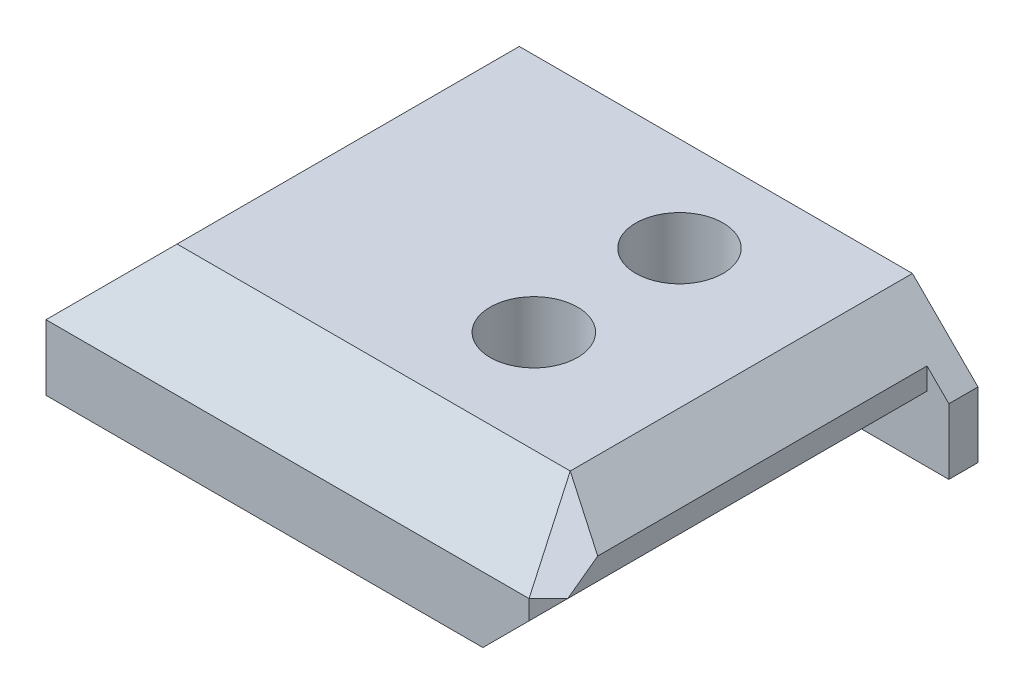
SolidWorks part; units mm, degrees
ref_plane "Front Plane" through (0, 0, 0) normal (0, 0, 1) x (1, 0, 0)
ref_plane "Top Plane" through (0, 0, 0) normal (0, 1, 0) x (1, 0, 0)
ref_plane "Right Plane" through (0, 0, 0) normal (1, 0, 0) x (0, 0, -1)
sketch "Sketch1" plane through (0, 0, 0) normal (0, 0, 1) x (1, 0, 0)
  line L0 (0, 0) -> (0, 9)
  line L1 (0, 9) -> (36, 9)
  line L2 (36, 9) -> (36, 0)
  line L3 (55, 0) -> (-55, 0) construction
  line L4 (36, 0) -> (0, 0)
extrude "Boss-Extrude1" add sketch "Sketch1" along normal blind 28
ref_plane "Plane1" through (0, 4.5, 0) normal (0, -1, 0) x (-1, 0, 0)
sketch "Sketch2" plane through (0, 0, 0) normal (0, 0, 1) x (1, 0, 0)
  line L0 (0, 4.5) -> (4.5, 9)
  line L1 (0, 9) -> (0, 0) construction
  line L2 (36, 9) -> (0, 9) construction
  line L3 (0, 4.5) -> (0, 9)
  line L4 (0, 9) -> (4.5, 9)
  line L5 (18, 10.7859) -> (18, -2.0026) construction
  line L6 (36, 4.5) -> (31.5, 9)
  line L7 (36, 4.5) -> (36, 9)
  line L8 (36, 9) -> (31.5, 9)
extrude "Cut-Extrude1" cut sketch "Sketch2" along normal blind 28
sketch "Sketch3" plane through (0, 0, 0) normal (1, 0, 0) x (0, 0, -1)
  line L0 (-28, 4.5) -> (-23.5, 9)
  line L1 (-28, 4.5) -> (0, 4.5) construction
  line L2 (-28, 0) -> (-28, 4.5) construction
  line L3 (-28, 9) -> (0, 9) construction
  line L4 (-28, 4.5) -> (-28, 9)
  line L5 (-28, 9) -> (-23.5, 9)
extrude "Cut-Extrude2" cut sketch "Sketch3" along normal blind 36
ref_plane "Plane2" through (32, 0, 32) normal (0.7071, 0, 0.7071) x (0, 1, 0)
sketch "Sketch5" plane through (32, 0, 32) normal (0.7071, 0, 0.7071) x (0, 1, 0)
  line L0 (0, -15.4) -> (0, 15.4) construction
  line L1 (0, 1.8738) -> (11.4404, 1.8738)
  line L2 (0, 1.8738) -> (0, -13.7452)
  line L3 (0, -13.7452) -> (11.4404, -13.7452)
  line L4 (11.4404, 1.8738) -> (11.4404, -13.7452)
extrude "Cut-Extrude4" cut sketch "Sketch5" against normal blind 2
ref_plane "Plane3" through (4, 0, -4) normal (-0.7071, 0, 0.7071) x (0.5774, -0.5774, 0.5774)
sketch "Sketch6" plane through (4, 0, -4) normal (-0.7071, 0, 0.7071) x (0.5774, -0.5774, 0.5774)
  line L0 (26.5581, 29.8021) -> (32.7193, 28.6474)
  line L1 (32.7193, 28.6474) -> (30.1986, 32.2123)
  line L2 (30.1986, 32.2123) -> (26.5581, 29.8021)
extrude "Cut-Extrude5" cut sketch "Sketch6" against normal blind 2 and the other way blind 2
sketch "Sketch7" plane through (0, 0, 0) normal (0, 0, 1) x (1, 0, 0)
  line L0 (0, 0) -> (5, 0) construction
  line L1 (15.4226, 0) -> (-15.4226, 0) construction
  line L2 (5, 0) -> (5, 3)
  line L3 (5, 0) -> (13.8116, 0)
  line L4 (13.8116, 0) -> (13.8116, 3)
  line L5 (5, 3) -> (5.7071, 3.7071)
  line L9 (13.8116, 3) -> (13.1045, 3.7071)
  line L10 (5.7071, 3.7071) -> (13.1045, 3.7071)
extrude "Cut-Extrude6" cut sketch "Sketch7" along normal blind 26
ref_plane "Plane5" through (0, 0, 28) normal (0, 0, 1) x (1, 0, 0)
sketch "Sketch8" plane through (0, 0, 28) normal (0, 0, 1) x (1, 0, 0)
  line L1 (15.4, 0) -> (-15.4, 0) construction
  line L2 (36, 0) -> (36, 4.5) construction
  line L3 (36, 0) -> (30, 0)
  line L5 (31.5, 9) -> (36, 4.5) construction
  line L8 (34.5, 4.5) -> (34.5, 6)
  line L9 (33.1716, 4.5) -> (36, 4.5) construction
  line L10 (34.5, 6) -> (36, 6)
  line L11 (36, 6) -> (36, 0)
  line L12 (34.5, 4.5) -> (30, 0)
extrude "Cut-Extrude7" cut sketch "Sketch8" against normal blind 26
sketch "Sketch9" plane through (0, 0, 0) normal (0, 1, 0) x (1, 0, 0)
  line L0 (0, -6.5) -> (19, -6.5) construction
  line L1 (0, -4.95) -> (0, 4.95) construction
  line L2 (5.7775, 0) -> (5.7775, -6.5) construction
  line L3 (-6.8862, 0) -> (6.8862, 0) construction
  line L4 (19, -6.5) -> (22, -6.5)
  circle A0 centre (22, -6.5) radius 3
sketch "Sketch10" plane through (0, 9, 0) normal (0, 1, 0) x (1, 0, 0)
  circle A0 centre (22, -6.5) radius 3
extrude "Cut-Extrude8" cut sketch "Sketch10" against normal blind 7
sketch "Sketch11" plane through (0, 2, 0) normal (0, 1, 0) x (1, 0, 0)
  circle A0 centre (22, -6.5) radius 1.5
extrude "Cut-Extrude9" cut sketch "Sketch11" against normal up to surface (2 mm away) up to face at (16.9623, 0, 11.2)
sketch "Sketch12" plane through (0, 0, 0) normal (0, 1, 0) x (1, 0, 0)
  line L0 (22, -8) -> (22, -15) construction
  line L1 (22, -15) -> (22, -16.5)
  circle A0 centre (22, -6.5) radius 1.5 construction
  circle A1 centre (22, -16.5) radius 1.5
extrude "Cut-Extrude10" cut sketch "Sketch12" along normal up to surface (9 mm away) contours A1 region at (20.9693, 0, 17.5307) up to face at (22, 9, 9.5)
sketch "Sketch13" plane through (0, 9, 0) normal (0, 1, 0) x (1, 0, 0)
  circle A0 centre (22, -16.5) radius 3
extrude "Cut-Extrude11" cut sketch "Sketch13" against normal blind 7
